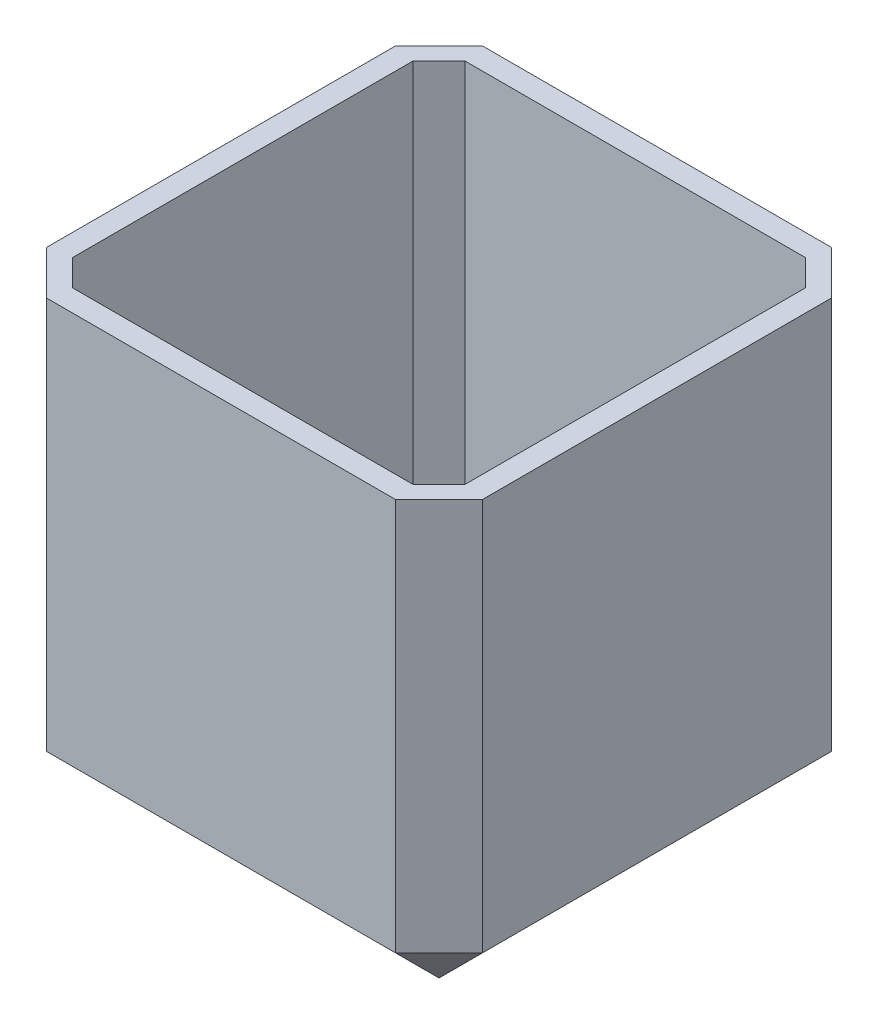
SolidWorks part; units mm, degrees
ref_plane "Front Plane" through (0, 0, 0) normal (0, 0, 1) x (1, 0, 0)
ref_plane "Top Plane" through (0, 0, 0) normal (0, 1, 0) x (1, 0, 0)
ref_plane "Right Plane" through (0, 0, 0) normal (1, 0, 0) x (0, 0, -1)
sketch "Sketch1" plane through (0, 0, 0) normal (0, 1, 0) x (1, 0, 0)
  line L1 (-25, -25) -> (25, -25)
  line L2 (-25, -25) -> (-25, 25)
  line L3 (-25, 25) -> (25, 25)
  line L4 (25, -25) -> (25, 25)
  line L5 (-25, -25) -> (25, 25) construction
  line L6 (-25, 25) -> (25, -25) construction
  point P0 (0, 0)
  dimension "D1" = 50
  dimension "D2" = 50
extrude "Boss-Extrude1" add sketch "Sketch1" along normal blind 50
sketch "Sketch2" plane through (0, 50, 0) normal (0, 1, 0) x (1, 0, 0)
  line L1 (-22.5, -22.5) -> (22.5, -22.5)
  line L2 (-22.5, -22.5) -> (-22.5, 22.5)
  line L3 (-22.5, 22.5) -> (22.5, 22.5)
  line L4 (22.5, -22.5) -> (22.5, 22.5)
  line L5 (-22.5, -22.5) -> (22.5, 22.5) construction
  line L6 (-22.5, 22.5) -> (22.5, -22.5) construction
  point P0 (0, 0)
  dimension "D1" = 45
  dimension "D2" = 45
extrude "Cut-Extrude1" cut sketch "Sketch2" against normal offset from surface (45 mm away) 5 up to face at (0, 0, 0)
fillet "Fillet2" radius 5 8 edges at (-25, 25, -25) (-25, 0, 0) (0, 0, -25) (25, 25, -25) (25, 0, 0) (0, 0, 25) (-25, 25, 25) (25, 25, 25) profile chamfer
fillet "Fillet3" radius 3 4 edges at (-22.5, 27.5, 22.5) (-22.5, 27.5, -22.5) (22.5, 27.5, 22.5) (22.5, 27.5, -22.5) profile chamfer
